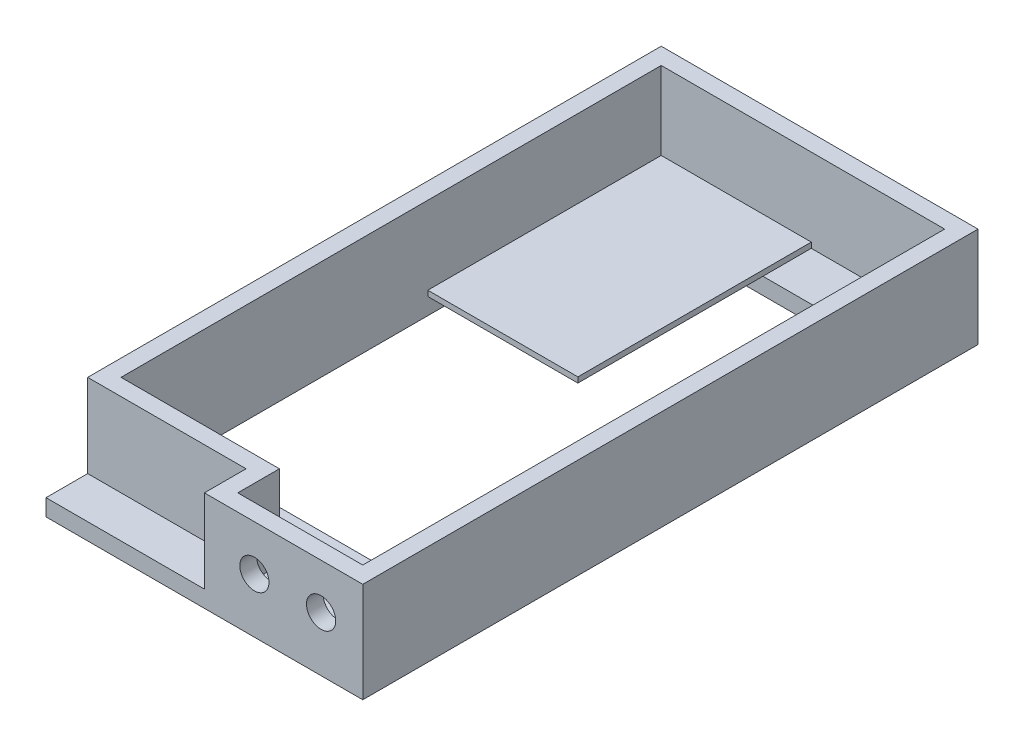
SolidWorks part; units mm, degrees
ref_plane "Front Plane" through (0, 0, 0) normal (0, 0, 1) x (1, 0, 0)
ref_plane "Top Plane" through (0, 0, 0) normal (0, 1, 0) x (1, 0, 0)
ref_plane "Right Plane" through (0, 0, 0) normal (1, 0, 0) x (0, 0, -1)
ref_axis "X-Axis" through (-88.99, 0, 0) along (1, 0, 0)
ref_axis "Y-Axis" through (0, 55, 0) along (0, -1, 0)
ref_axis "Z-Axis" through (0, 0, -88.99) along (0, 0, 1)
sketch "Sketch1" plane through (0, 0, 0) normal (0, 1, 0) x (1, 0, 0)
  line L1 (-19, -36.9) -> (19, -36.9)
  line L2 (-19, -36.9) -> (-19, 36.9)
  line L3 (-19, 36.9) -> (19, 36.9)
  line L4 (19, -36.9) -> (19, 36.9)
  line L5 (-19, -36.9) -> (19, 36.9) construction
  line L6 (-19, 36.9) -> (19, -36.9) construction
  point P0 (0, 0)
  dimension "D1" = 38
  dimension "D2" = 73.8
extrude "Boss-Extrude1" add sketch "Sketch1" along normal blind 12
sketch "Sketch2" plane through (0, 12, 0) normal (0, 1, 0) x (1, 0, 0)
  line L1 (-19, -36.9) -> (0, -36.9)
  line L2 (-19, -36.9) -> (-19, -31.9)
  line L3 (-19, -31.9) -> (0, -31.9)
  line L4 (0, -36.9) -> (0, -31.9)
  dimension "D1" = 5
  dimension "D2" = 19
extrude "Cut-Extrude1" cut sketch "Sketch2" against normal offset from surface (10 mm away) 2 up to face at (0, 0, 0)
sketch "Sketch6" plane through (0, 12, 0) normal (0, 1, 0) x (1, 0, 0)
  line L0 (19, 36.9) -> (-19, 36.9) construction
  line L1 (-4.5, 36.9) -> (0.5, 36.9)
  line L2 (-4.5, 36.9) -> (-4.5, 35.4)
  line L3 (-4.5, 35.4) -> (0.5, 35.4)
  line L4 (0.5, 36.9) -> (0.5, 35.4)
  line L5 (-19, 36.9) -> (-19, -31.9) construction
  dimension "D1" = 5
  dimension "D2" = 1.5
  dimension "D3" = 14.5
extrude "Cut-Extrude4" [suppressed] cut sketch "Sketch6" against normal offset from surface (8 mm away) 4 up to face at (0, 0, 0)
sketch "Sketch7" [suppressed] plane through (0, 12, 0) normal (0, 1, 0) x (1, 0, 0)
  line L0 (-3, 38.5) -> (-3, 37.68) construction
  line L1 (-5.5, 38.5) -> (-0.5, 38.5) construction
  line L3 (-7.1, 36.86) -> (1.1, 36.86)
  line L4 (-7.1, 36.86) -> (-7.1, 38.5)
  line L5 (-7.1, 38.5) -> (1.1, 38.5)
  line L6 (1.1, 36.86) -> (1.1, 38.5)
  line L7 (-7.1, 36.86) -> (1.1, 38.5) construction
  line L8 (-7.1, 38.5) -> (1.1, 36.86) construction
  dimension "D1" = 1.84
  dimension "D2" = 8.2
extrude "Cut-Extrude5" [suppressed] cut sketch "Sketch7" against normal offset from surface (9.6 mm away) 1.6 up to face at (0, 12, 10.6333) offset beyond the face yes
shell "Shell1" thickness 2 removed face at (0, 12, 10.6333)
sketch "Sketch8" [suppressed] plane through (0, 12, 0) normal (0, 1, 0) x (1, 0, 0)
  line L0 (-5.5, 38.5) -> (-5.5, 34.86) construction
  line L1 (-9.1, 34.86) -> (3.1, 34.86) construction
  line L3 (-5.5, 34.86) -> (-0.5, 34.86)
  line L4 (-5.5, 34.86) -> (-5.5, 38.5)
  line L5 (-5.5, 38.5) -> (-0.5, 38.5)
  line L6 (-0.5, 34.86) -> (-0.5, 38.5)
extrude "Cut-Extrude6" [suppressed] cut sketch "Sketch8" against normal up to surface (8 mm away) up to face at (0.6667, 12, 9.9667)
sketch "Sketch9" plane through (0, 0, 36.9) normal (0, 0, 1) x (1, 0, 0)
  line L0 (-19, 0) -> (19, 0) construction
  circle A0 centre (10, 6.5) radius 5
  dimension "D1" = 10
  dimension "D2" = 6.5
  dimension "D3" = 7
extrude "Cut-Extrude7" [suppressed] cut sketch "Sketch9" against normal blind 44 from offset 10 offset against normal yes
sketch "Sketch10" plane through (0, 0, -36.9) normal (0, 0, -1) x (-1, 0, 0)
  line L0 (19, 2.1) -> (8, 2.1) construction
  line L1 (19, 12) -> (19, 0) construction
  line L2 (8, 2.1) -> (8, -1.9) construction
  line L3 (12.25, 2.1) -> (3.75, 2.1)
  line L4 (11.5, -1.9) -> (4.5, -1.9)
  line L5 (3.75, 2.1) -> (4.5, -1.9)
  line L6 (11.5, -1.9) -> (12.25, 2.1)
  line L7 (-19, 0) -> (19, 0) construction
  point P8 (8, 2.1)
  point P10 (8, -1.9)
  dimension "D1" = 4
  dimension "D2" = 7
  dimension "D3" = 8.5
  dimension "D4" = 11
  dimension "D5" = 2.1
extrude "Cut-Extrude8" [suppressed] cut sketch "Sketch10" against normal through all
fillet "Fillet1" [suppressed] radius 0.9
fillet "Fillet2" [suppressed] radius 1
sketch "Sketch11" plane through (0, 2, 0) normal (0, 1, 0) x (1, 0, 0)
  line L1 (-17, 34.9) -> (1, 34.9)
  line L2 (-17, 34.9) -> (-17, 6.9)
  line L3 (-17, 6.9) -> (1, 6.9)
  line L4 (1, 34.9) -> (1, 6.9)
  dimension "D1" = 18
  dimension "D2" = 28
extrude "Boss-Extrude2" add sketch "Sketch11" along normal blind 0.65
sketch "Sketch12" plane through (0, 0, 36.9) normal (0, 0, 1) x (1, 0, 0)
  line L0 (19, 6.5686) -> (0, 6.5686) construction
  line L1 (19, 12) -> (19, 0) construction
  line L2 (0, 2) -> (0, 12) construction
  circle A0 centre (6, 6.5686) radius 1.75
  circle A1 centre (14, 6.5686) radius 1.75
  dimension "D1" = 3.5
  dimension "D2" = 5
  dimension "D3" = 8
extrude "Cut-Extrude9" cut sketch "Sketch12" against normal up to next
sketch "Sketch13" plane through (0, 0, 0) normal (0, -1, 0) x (1, 0, 0)
  line L0 (-19, 36.9) -> (19, 36.9) construction
  line L1 (17, 23.9) -> (-17, 23.9)
  line L2 (17, 23.9) -> (17, -29.1)
  line L3 (17, -29.1) -> (-17, -29.1)
  line L4 (-17, 23.9) -> (-17, -29.1)
  line L6 (-17, 23.9) -> (-19, 23.9) construction
  line L8 (17, 23.9) -> (19, 23.9) construction
  line L9 (19, 36.9) -> (19, -36.9) construction
  line L10 (-19, -36.9) -> (-19, 36.9) construction
  dimension "D1" = 53
  dimension "D2" = 13
  dimension "D4" = 34
extrude "Cut-Extrude10" cut sketch "Sketch13" against normal up to surface (2 mm away) up to face at (0.75, 2, 5.75)
equation "\"D2@Sketch7\"=\"D1@Sketch6\"+(1.6*2)"
equation "\"D2@Sketch9\"=(\"D1@Sketch9\"/2)+\"D1@Cut-Extrude1\"-0.5"
equation "\"D3@Sketch9\"=(\"D1@Sketch9\"/2)+2"
